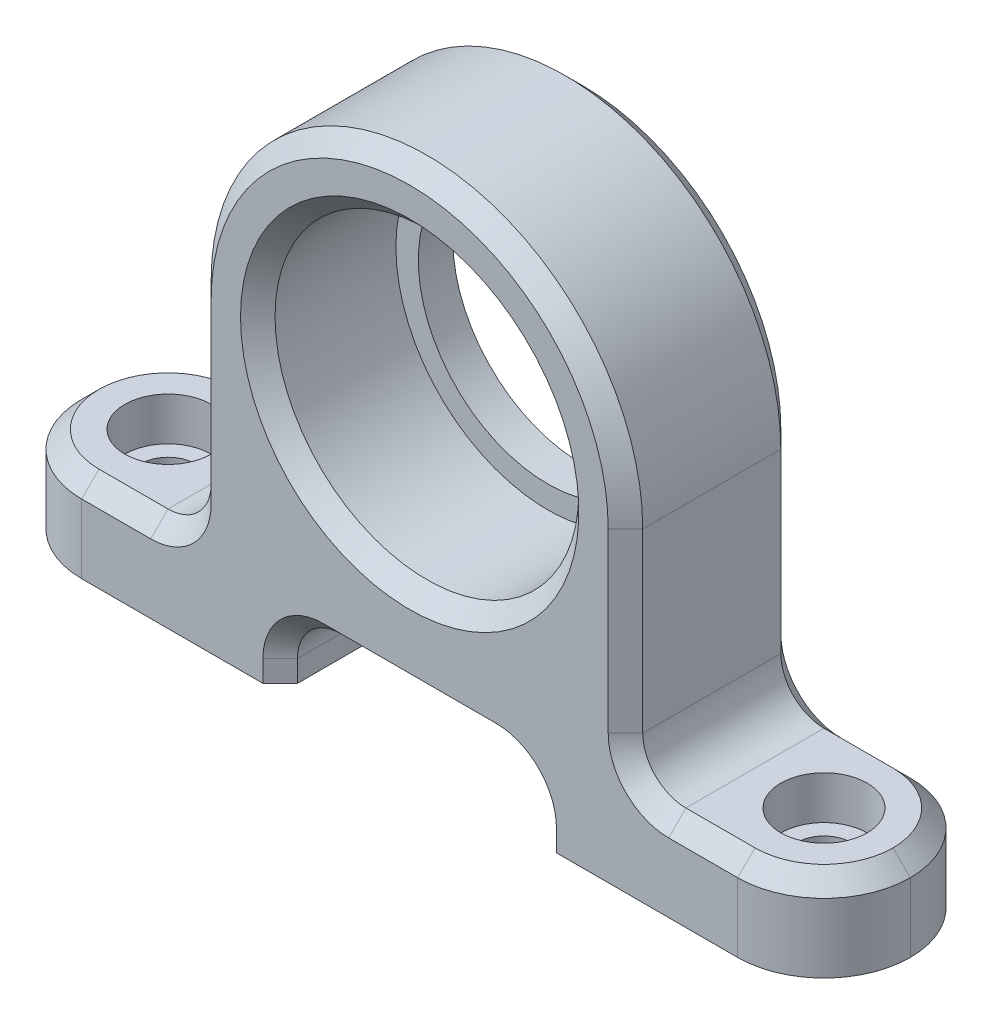
SolidWorks part; units mm, degrees
ref_plane "前视基准面" through (0, 0, 0) normal (0, 0, 1) x (1, 0, 0)
ref_plane "上视基准面" through (0, 0, 0) normal (0, 1, 0) x (1, 0, 0)
ref_plane "右视基准面" through (0, 0, 0) normal (1, 0, 0) x (0, 0, -1)
sketch "草图1" plane through (0, 0, 0) normal (0, 1, 0) x (1, 0, 0)
  line L1 (-48, 10) -> (48, 10)
  line L2 (-48, 10) -> (-48, -10)
  line L3 (-48, -10) -> (48, -10)
  line L4 (48, 10) -> (48, -10)
  line L5 (-48, 10) -> (48, -10) construction
  line L6 (-48, -10) -> (48, 10) construction
  point P0 (0, 0)
extrude "凸台-拉伸1" add sketch "草图1" along normal blind 10 contours L2 L3 L4 L1
sketch "草图2" plane through (0, 10, 0) normal (0, 1, 0) x (1, 0, 0)
  line L0 (-48, 0) -> (-38, 0) construction
  line L1 (-48, 10) -> (-48, -10) construction
  line L2 (0, 0) -> (0, 10) construction
  line L3 (-48, 10) -> (48, 10) construction
  circle A0 centre (-38, 0) radius 5
  circle A1 centre (38, 0) radius 5
extrude "切除-拉伸1" cut sketch "草图2" against normal blind 5
fillet "圆角1" radius 10 4 edges at (48, 5, -10) (48, 5, 10) (-48, 5, 10) (-48, 5, -10)
sketch "草图3" plane through (0, 5, 0) normal (0, 1, 0) x (1, 0, 0)
  circle A0 centre (-38, 0) radius 3.1
  circle A1 centre (38, 0) radius 3.1
extrude "切除-拉伸2" cut sketch "草图3" against normal blind 5
chamfer "倒角1" distance 1 angle 45 2 edges at (38, 0, 3.1) (-38, 0, 3.1)
sketch "草图4" plane through (0, 10, 0) normal (0, 1, 0) x (1, 0, 0)
  line L0 (-38, 10) -> (38, 10) construction
  line L1 (-25, -10) -> (25, -10)
  line L2 (-25, -10) -> (-25, 10)
  line L3 (-25, 10) -> (25, 10)
  line L4 (25, -10) -> (25, 10)
  line L5 (-25, -10) -> (25, 10) construction
  line L6 (-25, 10) -> (25, -10) construction
  point P0 (0, 0)
extrude "凸台-拉伸2" add sketch "草图4" along normal blind 50.5
sketch "草图6" plane through (0, 0, 10) normal (0, 0, 1) x (1, 0, 0)
  line L0 (0, 0) -> (0, 60.5) construction
  line L2 (-25, 60.5) -> (25, 60.5) construction
  line L3 (0, 60.5) -> (0, 35.5) construction
  arc A0 (25, 35.5) -> (-25, 35.5) centre (0, 35.5) ccw
extrude "切除-拉伸4" cut sketch "草图6" against normal through all and the other way through all flip side to cut contours A0
sketch "草图7" plane through (0, 0, 10) normal (0, 0, 1) x (1, 0, 0)
  circle A0 centre (0, 35.5) radius 17.6
extrude "切除-拉伸5" cut sketch "草图7" against normal blind 16
sketch "草图8" plane through (0, 0, -6) normal (0, 0, 1) x (1, 0, 0)
  circle A0 centre (0, 35.5) radius 15
extrude "切除-拉伸6" cut sketch "草图8" against normal blind 16
chamfer "倒角3" distance 2 angle 45 1 edges at (17.6, 35.5, 10)
fillet "圆角3" radius 5 2 edges at (25, 10, 0) (-25, 10, 0)
chamfer "倒角5" distance 2 angle 45 18 edges at (0, 60.5, -10) (25, 25.25, -10) (-25, 25.25, -10) (26.4645, 11.4645, -10) (-26.4645, 11.4645, -10) (34, 10, -10) (-34, 10, -10) (45.0711, 10, -7.0711) (-45.0711, 10, -7.0711) (45.0711, 10, 7.0711) (-45.0711, 10, 7.0711) (34, 10, 10) (-34, 10, 10) (26.4645, 11.4645, 10) (-26.4645, 11.4645, 10) (25, 25.25, 10) (-25, 25.25, 10) (0, 60.5, 10)
sketch "草图9" plane through (0, 0, 10) normal (0, 0, 1) x (1, 0, 0)
  line L1 (-15, 7.5) -> (15, 7.5)
  line L2 (-15, 7.5) -> (-15, -7.5)
  line L3 (-15, -7.5) -> (15, -7.5)
  line L4 (15, 7.5) -> (15, -7.5)
  line L5 (-15, 7.5) -> (15, -7.5) construction
  line L6 (-15, -7.5) -> (15, 7.5) construction
  point P0 (0, 0)
extrude "切除-拉伸7" cut sketch "草图9" against normal through all
fillet "圆角4" radius 5 2 edges at (15, 7.5, 0) (-15, 7.5, 0)
chamfer "倒角6" distance 2 angle 45 10 edges at (15, 1.25, -10) (13.5355, 6.0355, -10) (0, 7.5, -10) (-15, 1.25, -10) (-13.5355, 6.0355, -10) (15, 1.25, 10) (13.5355, 6.0355, 10) (-15, 1.25, 10) (0, 7.5, 10) (-13.5355, 6.0355, 10)
